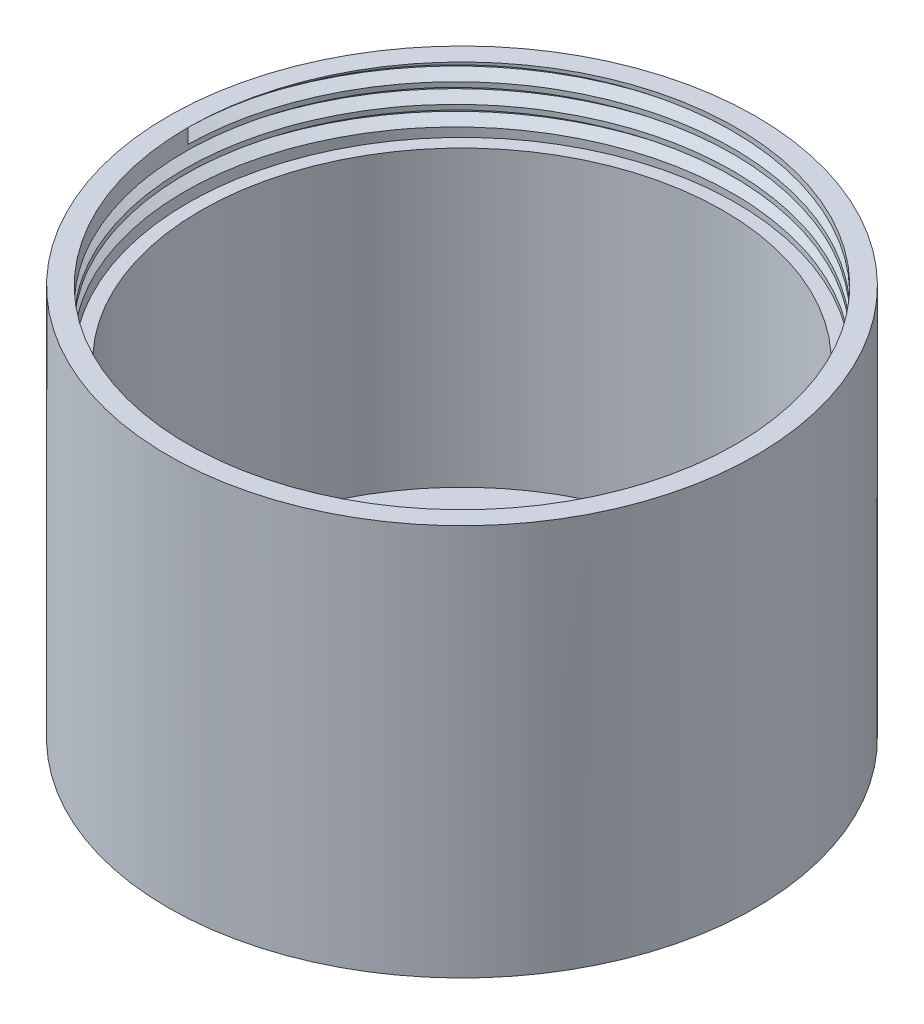
SolidWorks part; units mm, degrees
ref_plane "Front Plane" through (0, 0, 0) normal (0, 0, 1) x (1, 0, 0)
ref_plane "Top Plane" through (0, 0, 0) normal (0, 1, 0) x (1, 0, 0)
ref_plane "Right Plane" through (0, 0, 0) normal (1, 0, 0) x (0, 0, -1)
sketch "Sketch1" plane through (0, 0, 0) normal (0, 1, 0) x (1, 0, 0)
  circle A0 centre (0, 0) radius 45
  dimension "D1" = 90
extrude "Boss-Extrude1" add sketch "Sketch1" along normal blind 50
shell "Shell1" thickness 5 removed face at (0, 50, 45)
sketch "Sketch7" plane through (0, 0, 0) normal (1, 0, 0) x (0, 0, -1)
  line L0 (0, 0) -> (0, 55.2649) construction
  line L1 (-45, 50) -> (-42, 50)
  line L2 (-45, 50) -> (-45, 60)
  line L3 (-45, 60) -> (-42, 60)
  line L4 (-42, 50) -> (-42, 60)
  dimension "D1" = 10
  dimension "D2" = 3
revolve "Revolve2" add sketch "Sketch7" angle 360 about L0
thread "Thread2" pitch 3 method cut profile "Thread Profile2" start angle 0, offset 0, length 8, pitch 3, diameter 84
ref_plane "Plane2" through (-42, 60, 0) normal (0, 0, 1) x (-1, 0, 0)
sketch "Thread Profile2" plane through (-42, 60, 0) normal (0, 0, 1) x (-1, 0, 0)
  line L0 (0, 0) -> (0, 3) construction
  line L1 (0, 0) -> (1.6238, 0.9375)
  line L2 (1.6238, 0.9375) -> (1.6238, 1.3125)
  line L3 (1.6238, 1.3125) -> (0, 2.25)
  line L4 (1.6238, 1.125) -> (0, 1.125) construction
  line L11 (0, 0) -> (0, 2.25)
  point P2 (0, 0)
  dimension "Pitch" = 3
  dimension "Profile_Angle" = 60
  dimension "Profile_Land" = 0.375
  dimension "Profile_Height" = 1.6238
